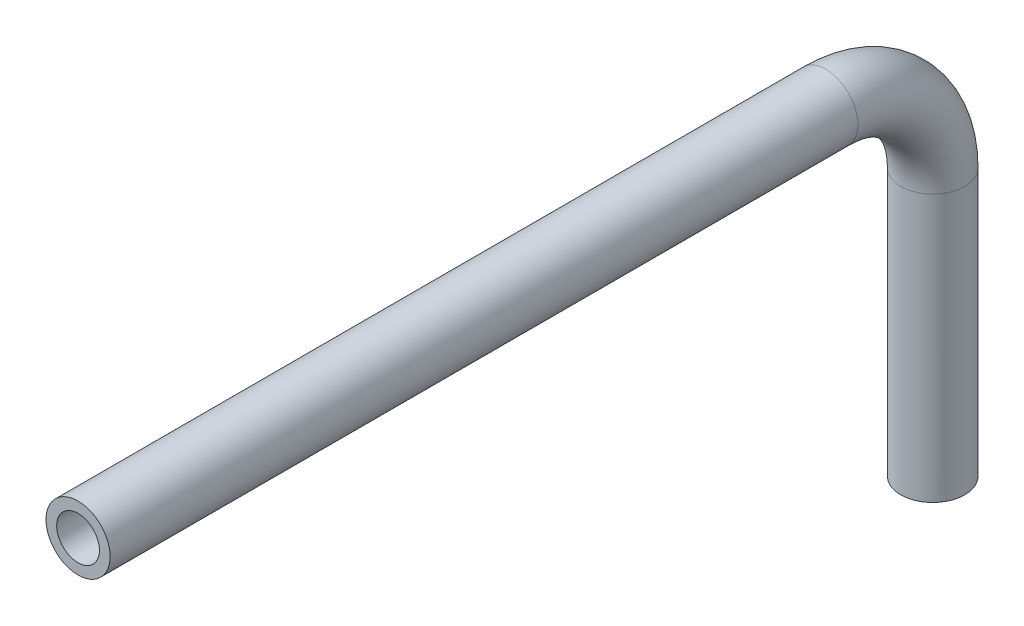
SolidWorks part; units mm, degrees
ref_plane "Front Plane" through (0, 0, 0) normal (0, 0, 1) x (1, 0, 0)
ref_plane "Top Plane" through (0, 0, 0) normal (0, 1, 0) x (1, 0, 0)
ref_plane "Right Plane" through (0, 0, 0) normal (1, 0, 0) x (0, 0, -1)
sketch "Sketch1" plane through (0, 0, 0) normal (1, 0, 0) x (0, 0, -1)
  line L0 (0, 0) -> (700, 0)
  line L1 (800, -100) -> (800, -350)
  arc A0 (700, 0) -> (800, -100) centre (700, -100) cw
  point P6 (800, 0)
  dimension "D3" = 100
  dimension "D1" = 800
  dimension "D2" = 350
sweep "Sweep-Thin1" add path "Sketch1" circular profile diameter 60 parameters "D1"=10, "D3"=60
